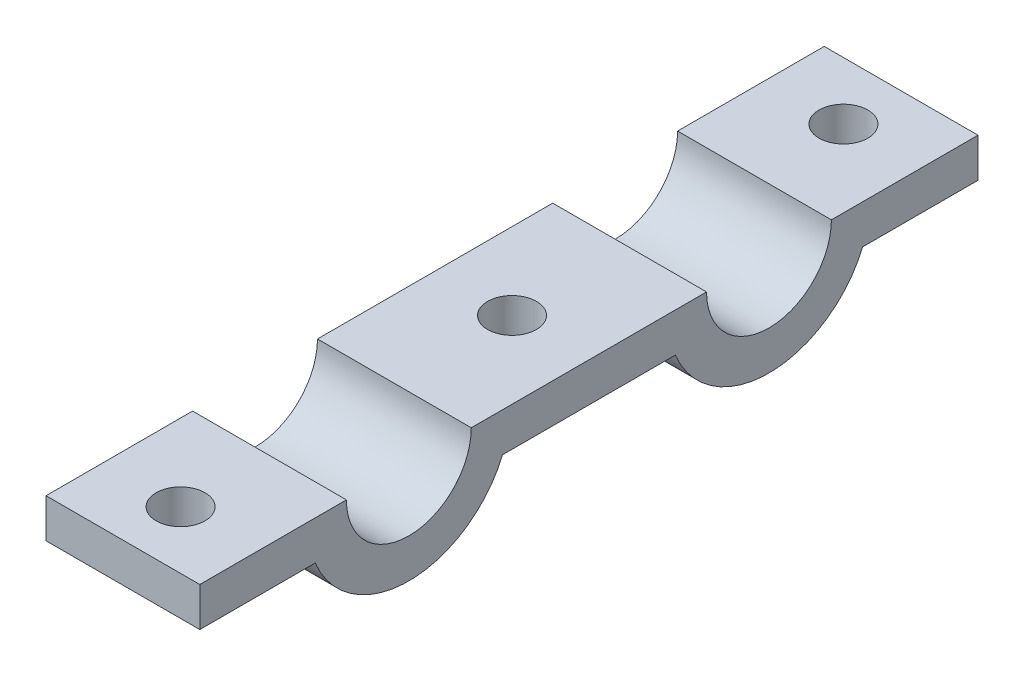
SolidWorks part; units mm, degrees
ref_plane "Front Plane" through (0, 0, 0) normal (0, 0, 1) x (1, 0, 0)
ref_plane "Top Plane" through (0, 0, 0) normal (0, 1, 0) x (1, 0, 0)
ref_plane "Right Plane" through (0, 0, 0) normal (1, 0, 0) x (0, 0, -1)
sketch "Sketch2" plane through (0, 0, 0) normal (1, 0, 0) x (0, 0, -1)
  line L0 (-15.24, 0) -> (15.24, 0) construction
  line L1 (-16.24, 0) -> (-54.3667, 0)
  line L2 (16.24, 0) -> (77.4225, 0)
  line L3 (0, 0) -> (93.6625, 0) construction
  line L4 (109.9025, 0) -> (148.0292, 0)
  line L5 (-24.3667, -10.16) -> (-54.3667, -10.16)
  line L6 (24.3667, -10.16) -> (69.2958, -10.16)
  line L7 (118.0292, -10.16) -> (148.0292, -10.16)
  line L8 (-54.3667, 0) -> (-54.3667, -10.16)
  line L9 (148.0292, 0) -> (148.0292, -10.16)
  arc A0 (-15.24, 0) -> (15.24, 0) centre (0, 0) ccw construction
  arc A1 (-16.24, 0) -> (16.24, 0) centre (0, 0) ccw
  arc A2 (78.4225, 0) -> (108.9025, 0) centre (93.6625, 0) ccw construction
  arc A3 (77.4225, 0) -> (109.9025, 0) centre (93.6625, 0) ccw
  arc A4 (-24.3667, -10.16) -> (24.3667, -10.16) centre (0, 0) ccw
  arc A5 (69.2958, -10.16) -> (118.0292, -10.16) centre (93.6625, 0) ccw
  dimension "D6" = 10.16
  dimension "D1" = 30.48
  dimension "D3" = 93.6625
  dimension "D5" = 30
  dimension "D7" = 10.16
  dimension "D8" = 10.16
  dimension "D2" = 1
  dimension "D4" = 1
extrude "Boss-Extrude1" add sketch "Sketch2" along normal blind 40
sketch "Sketch3" plane through (0, 0, 0) normal (0, 1, 0) x (1, 0, 0)
  line L0 (0, -54.3667) -> (0, -24.3667) construction
  line L1 (0, -54.3667) -> (0, -24.3667) construction
  line L2 (40, -54.3667) -> (0, -54.3667) construction
  line L3 (40, -54.3667) -> (0, -54.3667) construction
  line L4 (40, 16.24) -> (0, 16.24) construction
  line L6 (40, 77.4225) -> (40, 16.24) construction
  line L7 (0, 77.4225) -> (0, 16.24) construction
  line L16 (40, 16.24) -> (0, 16.24) construction
  line L18 (40, 77.4225) -> (40, 16.24) construction
  line L19 (0, 77.4225) -> (0, 16.24) construction
  line L24 (0, 46.8313) -> (40, 46.8313) construction
  circle A0 centre (20, -39.3667) radius 6.35
  circle A1 centre (20, 133.0292) radius 6.35
  circle A2 centre (20, 46.8313) radius 6.35
  point P6 (0, -39.3667)
  point P14 (20, -54.3667)
  point P15 (0, 0)
  dimension "D1" = 12.7
extrude "Cut-Extrude1" cut sketch "Sketch3" against normal up to next
